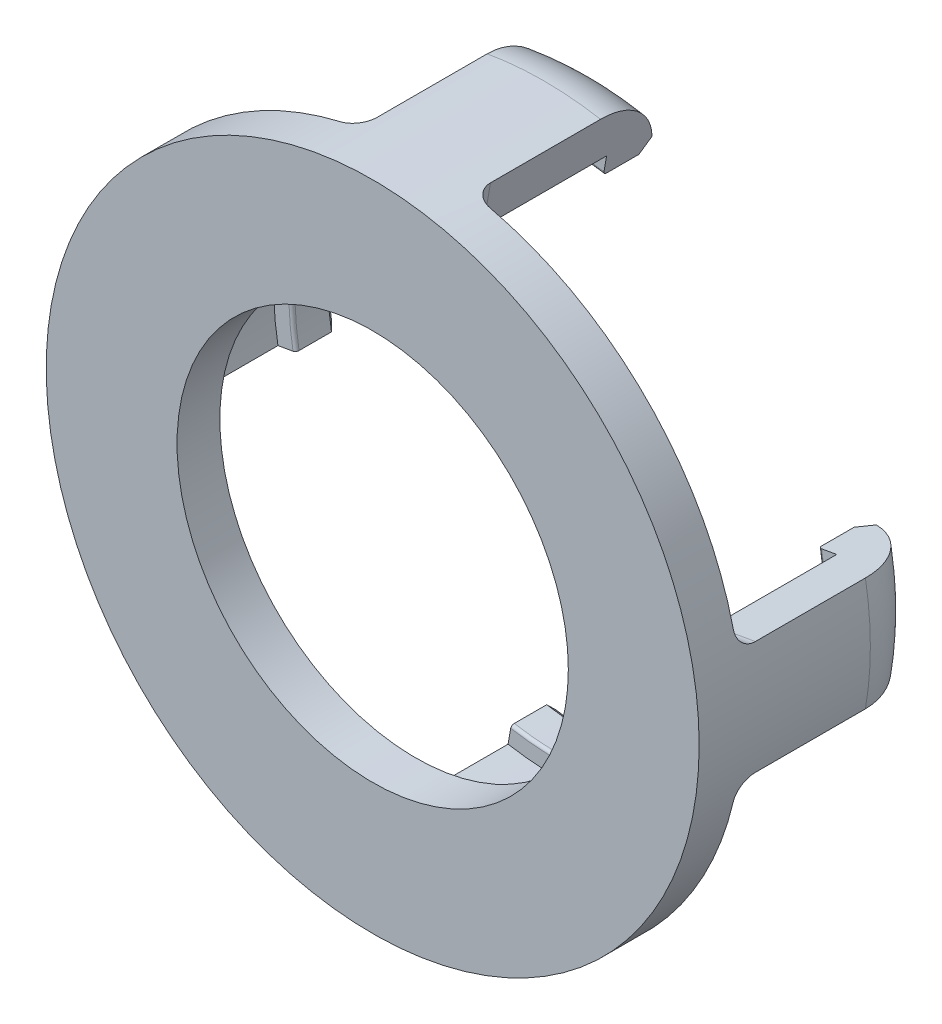
SolidWorks part; units mm, degrees
ref_plane "Front Plane" through (0, 0, 0) normal (0, 0, 1) x (1, 0, 0)
ref_plane "Top Plane" through (0, 0, 0) normal (0, 1, 0) x (1, 0, 0)
ref_plane "Right Plane" through (0, 0, 0) normal (1, 0, 0) x (0, 0, -1)
sketch "Sketch1" plane through (0, 0, 0) normal (0, 0, 1) x (1, 0, 0)
  circle A0 centre (0, 0) radius 16
  circle A1 centre (0, 0) radius 22.7 construction
  circle A2 centre (0, 0) radius 26.7
  dimension "D1" = 32
  dimension "D2" = 45.4
  dimension "D3" = 53.4
extrude "Boss-Extrude1" add sketch "Sketch1" along normal blind 3.5
ref_axis "Axis1" through (0, 0, -0.32) along (0, 0, 1)
sketch "Sketch6" plane through (0, 0, 0) normal (0, 0, 1) x (1, 0, 0)
  circle A0 centre (0, 0) radius 21.7 construction
  circle A1 centre (0, 0) radius 21.7
  circle A2 centre (0, 0) radius 26.7
  dimension "D1" = 43.4
extrude "Boss-Extrude2" add sketch "Sketch6" against normal blind 15.5
ref_plane "Plane2" through (0, 0, -15.5) normal (0, 0, -1) x (-1, 0, 0)
sketch "Sketch8" plane through (0, 0, -15.5) normal (0, 0, -1) x (-1, 0, 0)
  line L0 (-4.6364, -26.2944) -> (-3.7682, -21.3703)
  line L1 (-26.2944, -4.6364) -> (-21.3703, -3.7682)
  line L2 (-26.2944, 4.6364) -> (-21.3703, 3.7682)
  line L3 (-4.6364, 26.2944) -> (-3.7682, 21.3703)
  line L4 (4.6364, 26.2944) -> (3.7682, 21.3703)
  line L5 (26.2944, 4.6364) -> (21.3703, 3.7682)
  line L6 (26.2944, -4.6364) -> (21.3703, -3.7682)
  line L7 (4.6364, -26.2944) -> (3.7682, -21.3703)
  arc A0 (-26.2944, -4.6364) -> (-4.6364, -26.2944) centre (0, 0) ccw
  arc A1 (21.3703, 3.7682) -> (3.7682, 21.3703) centre (0, 0) ccw
  arc A2 (-4.6364, 26.2944) -> (-26.2944, 4.6364) centre (0, 0) ccw
  arc A3 (3.7682, -21.3703) -> (21.3703, -3.7682) centre (0, 0) ccw
  arc A4 (26.2944, 4.6364) -> (4.6364, 26.2944) centre (0, 0) ccw
  arc A5 (-21.3703, -3.7682) -> (-3.7682, -21.3703) centre (0, 0) ccw
  arc A6 (4.6364, -26.2944) -> (26.2944, -4.6364) centre (0, 0) ccw
  arc A8 (-3.7682, 21.3703) -> (-21.3703, 3.7682) centre (0, 0) ccw
  point P20 (0, 0)
  dimension "D1" = 4
extrude "Cut-Extrude2" cut sketch "Sketch8" against normal up to surface (15.5 mm away) up to face at (16, 0, 0)
ref_plane "Plane3" through (0, 0, 0) normal (-0.1736, -0.9848, 0) x (-0.9848, 0.1736, 0)
sketch "Sketch9" plane through (0, 0, 0) normal (-0.1736, -0.9848, 0) x (-0.9848, 0.1736, 0)
  line L0 (-1022.1372, 11.6) -> (48977.8628, 11.6) construction
  line L3 (-21.7, 0) -> (-23.2, 0)
  line L4 (-21.7, 0) -> (-21.7, 11.6)
  line L5 (-21.7, 11.6) -> (-23.2, 11.6)
  line L6 (-23.2, 0) -> (-23.2, 11.6)
  line L7 (-21.7, 0) -> (-26.7, 0) construction
  dimension "D1" = 11.6
  dimension "D2" = 1.5
revolve "Cut-Revolve2" cut sketch "Sketch9" angle 360 about axis through (0, 0, -0.32) along (0, 0, 1)
fillet "Fillet1" radius 0.25 4 edges at (0, -21.7, -11.6) (-21.7, 0, -11.6) (0, 21.7, -11.6) (21.7, 0, -11.6)
fillet "Fillet3" radius 1.5 8 edges at (-4.3325, -24.571, 0) (4.3325, -24.571, 0) (24.571, 4.3325, 0) (-24.571, 4.3325, 0) (-24.571, -4.3325, 0) (-4.3325, 24.571, 0) (4.3325, 24.571, 0) (24.571, -4.3325, 0)
fillet "Fillet4" radius 5 4 edges at (0, -26.7, -15.5) (-26.7, 0, -15.5) (0, 26.7, -15.5) (26.7, 0, -15.5)
chamfer "Chamfer1" distance 1 angle 45 4 edges at (-21.7, 0, -15.5) (0, 21.7, -15.5) (21.7, 0, -15.5) (0, -21.7, -15.5)
fillet "Fillet5" radius 1 4 edges at (0, -23.2, 0) (-23.2, 0, 0) (23.2, 0, 0) (0, 23.2, 0)
